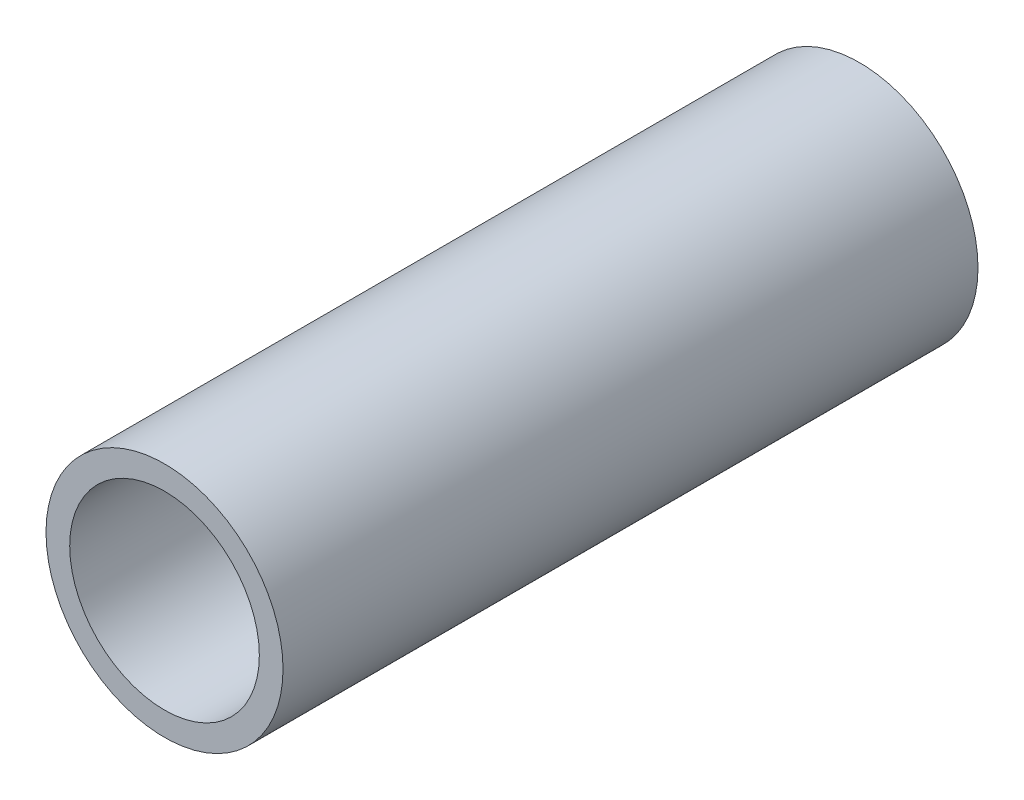
SolidWorks part; units mm, degrees
ref_plane "Front Plane" through (0, 0, 0) normal (0, 0, 1) x (1, 0, 0)
ref_plane "Top Plane" through (0, 0, 0) normal (0, 1, 0) x (1, 0, 0)
ref_plane "Right Plane" through (0, 0, 0) normal (1, 0, 0) x (0, 0, -1)
sketch "Sketch1" plane through (0, 0, 0) normal (0, 0, 1) x (1, 0, 0)
  circle A0 centre (0, 0) radius 1.25
  circle A1 centre (0, 0) radius 1
extrude "Boss-Extrude1" add sketch "Sketch1" along normal blind 7.33
